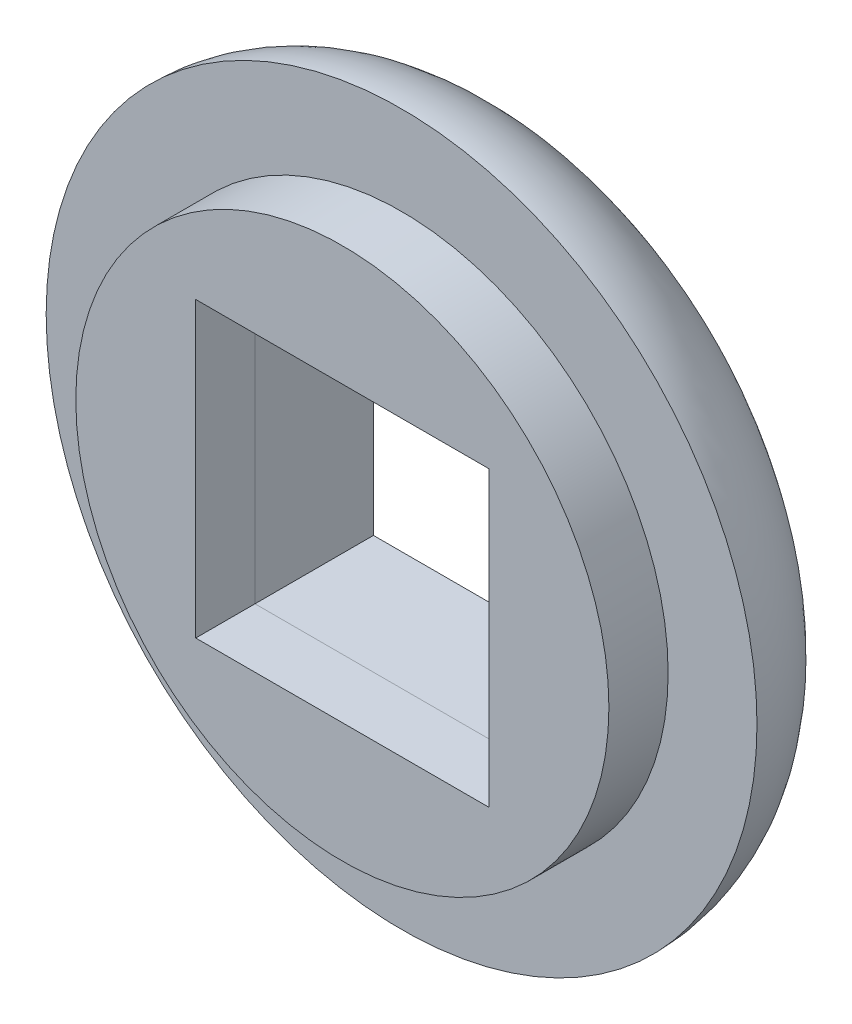
SolidWorks part; units mm, degrees
ref_plane "Front Plane" through (0, 0, 0) normal (0, 0, 1) x (1, 0, 0)
ref_plane "Top Plane" through (0, 0, 0) normal (0, 1, 0) x (1, 0, 0)
ref_plane "Right Plane" through (0, 0, 0) normal (1, 0, 0) x (0, 0, -1)
sketch "Sketch1" plane through (0, 0, 0) normal (0, 0, 1) x (1, 0, 0)
  line L1 (2.4749, 2.4749) -> (-2.4749, 2.4749)
  line L2 (2.4749, 2.4749) -> (2.4749, -2.4749)
  line L3 (2.4749, -2.4749) -> (-2.4749, -2.4749)
  line L4 (-2.4749, 2.4749) -> (-2.4749, -2.4749)
  line L5 (2.4749, 2.4749) -> (-2.4749, -2.4749) construction
  line L6 (2.4749, -2.4749) -> (-2.4749, 2.4749) construction
  circle A1 centre (0, 0) radius 4.5
  circle A2 centre (0, 0) radius 3.5 construction
  point P0 (0, 0)
  dimension "D1" = 9
extrude "Boss-Extrude1" add sketch "Sketch1" along normal blind 1
sketch "Sketch2" plane through (0, 0, 0) normal (0, 0, -1) x (-1, 0, 0)
  line L4 (2.4749, -2.4749) -> (2.4749, 2.4749)
  line L5 (-2.4749, -2.4749) -> (2.4749, -2.4749)
  line L6 (-2.4749, 2.4749) -> (-2.4749, -2.4749)
  line L7 (2.4749, 2.4749) -> (-2.4749, 2.4749)
  line L8 (2.4749, -2.4749) -> (2.4749, 2.4749)
  line L9 (-2.4749, -2.4749) -> (2.4749, -2.4749)
  line L10 (-2.4749, 2.4749) -> (-2.4749, -2.4749)
  line L11 (2.4749, 2.4749) -> (-2.4749, 2.4749)
  circle A0 centre (0, 0) radius 6 construction
  circle A3 centre (0, 0) radius 6
  dimension "D1" = 0
extrude "Boss-Extrude2" add sketch "Sketch2" along normal blind 2 separate body
fillet "Fillet1" radius 2 1 edges at (-6, 0, -2)
